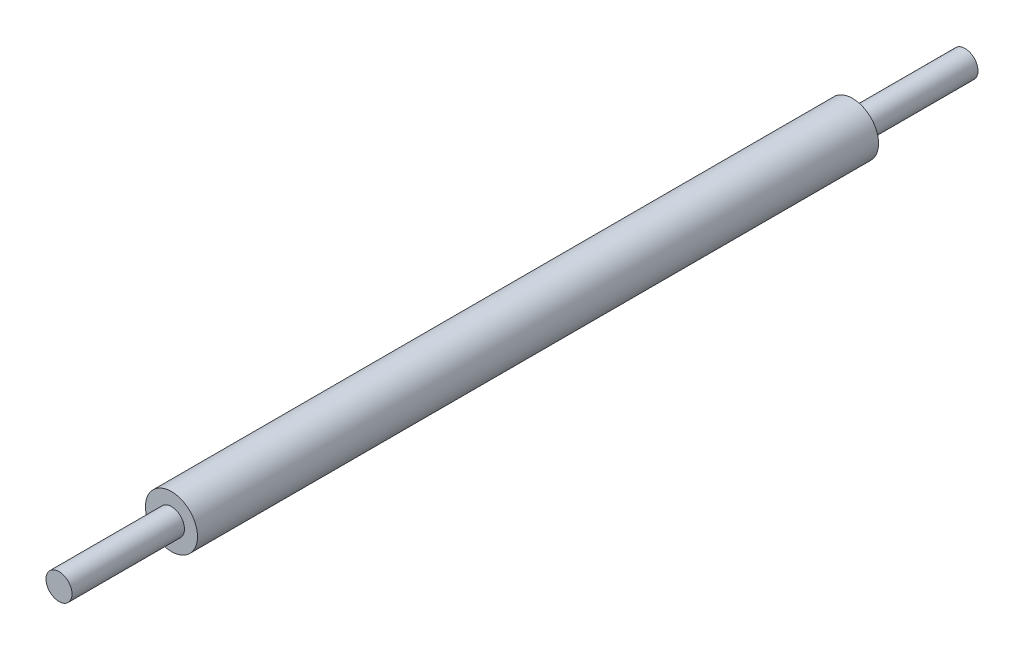
SolidWorks part; units mm, degrees
material "AISI 1010 Steel, hot rolled bar"
ref_plane "Front Plane" through (0, 0, 0) normal (0, 0, 1) x (1, 0, 0)
ref_plane "Top Plane" through (0, 0, 0) normal (0, 1, 0) x (1, 0, 0)
ref_plane "Right Plane" through (0, 0, 0) normal (1, 0, 0) x (0, 0, -1)
sketch "Sketch2" plane through (0, 0, 0) normal (0, 0, 1) x (1, 0, 0)
  circle A0 centre (0, 0) radius 6.35
  dimension "D1" = 12.7
extrude "Boss-Extrude1" add sketch "Sketch2" along normal blind 220.98
sketch "Sketch3" plane through (0, 0, 220.98) normal (0, 0, 1) x (1, 0, 0)
  circle A0 centre (0, 0) radius 6.35
extrude "Cut-Extrude1" cut sketch "Sketch3" against normal blind 26.416
sketch "Sketch4" plane through (0, 0, 194.564) normal (0, 0, 1) x (1, 0, 0)
  circle A0 centre (0, 0) radius 3.175
  dimension "D1" = 6.35
extrude "Boss-Extrude2" add sketch "Sketch4" along normal blind 26.416
sketch "Sketch5" plane through (0, 0, 0) normal (0, 0, -1) x (-1, 0, 0)
  circle A0 centre (0, 0) radius 6.35
extrude "Cut-Extrude2" cut sketch "Sketch5" against normal blind 26.416
sketch "Sketch6" plane through (0, 0, 26.416) normal (0, 0, -1) x (-1, 0, 0)
  circle A0 centre (0, 0) radius 3.175
  dimension "D1" = 6.35
extrude "Boss-Extrude3" add sketch "Sketch6" along normal blind 26.416
sketch "Sketch7" plane through (0, 0, 0) normal (0, 0, -1) x (-1, 0, 0)
  circle A0 centre (0, 0) radius 14.231
extrude "Cut-Extrude3" cut sketch "Sketch7" against normal blind 27.432
sketch "Sketch8" plane through (0, 0, 27.432) normal (0, 0, -1) x (-1, 0, 0)
  circle A0 centre (0, 0) radius 3.175
  dimension "D1" = 6.35
extrude "Boss-Extrude4" add sketch "Sketch8" along normal blind 27.432
sketch "Sketch9" plane through (0, 0, 220.98) normal (0, 0, 1) x (1, 0, 0)
  circle A0 centre (0, 0) radius 8.8374
extrude "Cut-Extrude4" cut sketch "Sketch9" against normal blind 27.432
sketch "Sketch10" plane through (0, 0, 193.548) normal (0, 0, 1) x (1, 0, 0)
  circle A0 centre (0, 0) radius 3.175
  dimension "D1" = 6.35
extrude "Boss-Extrude5" add sketch "Sketch10" along normal blind 27.432
